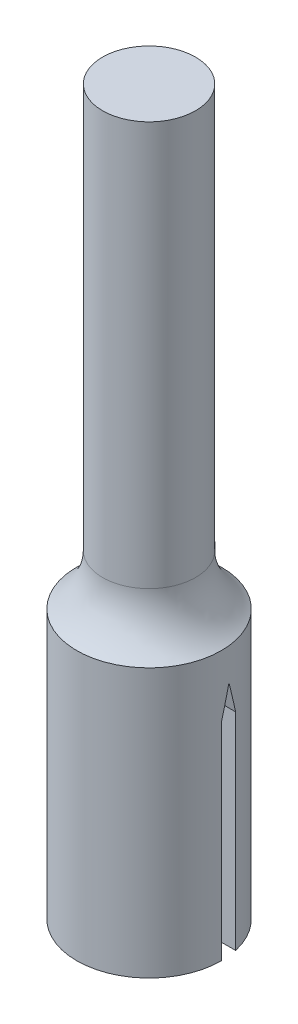
SolidWorks part; units mm, degrees
ref_plane "Front Plane" through (0, 0, 0) normal (0, 0, 1) x (1, 0, 0)
ref_plane "Top Plane" through (0, 0, 0) normal (0, 1, 0) x (1, 0, 0)
ref_plane "Right Plane" through (0, 0, 0) normal (1, 0, 0) x (0, 0, -1)
sketch "Sketch1" plane through (0, 0, 0) normal (0, 1, 0) x (1, 0, 0)
  circle A0 centre (0, 0) radius 2.25
  dimension "D1" = 4.5
extrude "Boss-Extrude1" add sketch "Sketch1" along normal blind 22
sketch "Sketch2" plane through (0, 0, 0) normal (0, -1, 0) x (1, 0, 0)
  circle A0 centre (0, 0) radius 3.5
  dimension "D1" = 7
extrude "Boss-Extrude2" add sketch "Sketch2" along normal blind 13
sketch "Sketch4" plane through (0, -13, 0) normal (0, -1, 0) x (1, 0, 0)
  circle A0 centre (0, 0) radius 1.5
  dimension "D1" = 3
extrude "Cut-Extrude2" cut sketch "Sketch4" against normal blind 10
sketch "Sketch5" plane through (0, -3, 0) normal (0, -1, 0) x (1, 0, 0)
  circle A0 centre (0, 0) radius 1.5
extrude "Cut-Extrude3" cut sketch "Sketch5" against normal blind 10 draft 22
sketch "Sketch6" plane through (0, -13, 0) normal (0, -1, 0) x (1, 0, 0)
  line L0 (0, 0) -> (-4.8621, 0)
  line L1 (0, 0) -> (5.7828, 0)
  line L2 (0, -0.7774) -> (5.7828, -0.7774)
  line L3 (5.7828, 0) -> (5.7828, -0.7774)
  line L4 (-4.8621, 0) -> (-4.8621, -0.7774)
  line L5 (-4.8621, -0.7774) -> (0, -0.7774)
extrude "Cut-Extrude4" cut sketch "Sketch6" against normal blind 10
fillet "Fillet2" radius 3 1 edges at (0, 0, -2.25)
sketch "Sketch7" plane through (0, -3, 0) normal (0, -1, 0) x (1, 0, 0)
  line L0 (0, 0) -> (6.1855, 0)
  line L1 (0, 0) -> (-4.7135, 0)
  line L2 (6.1855, 0) -> (6.1855, -0.7769)
  line L3 (0, -0.7769) -> (6.1855, -0.7769)
  line L4 (-4.7135, 0) -> (-4.7135, -0.7769)
  line L5 (-4.7135, -0.7769) -> (0, -0.7769)
extrude "Cut-Extrude5" cut sketch "Sketch7" against normal blind 10 draft 15
